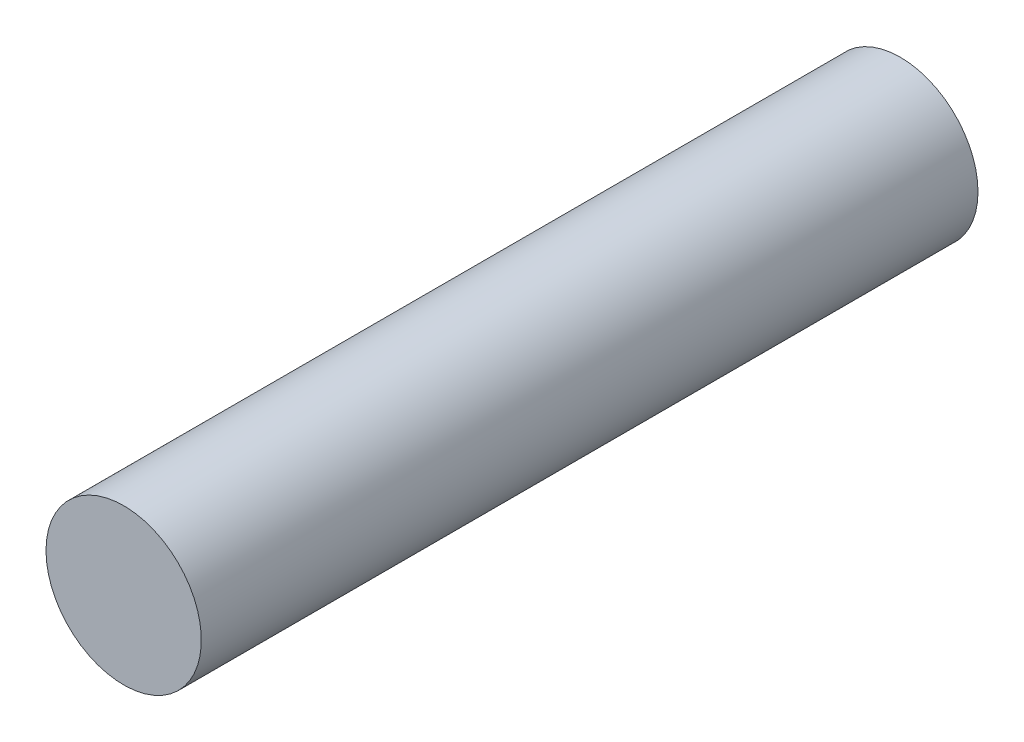
SolidWorks part; units mm, degrees
ref_plane "Front" through (0, 0, 0) normal (0, 0, 1) x (1, 0, 0)
ref_plane "Top" through (0, 0, 0) normal (0, 1, 0) x (1, 0, 0)
ref_plane "Right" through (0, 0, 0) normal (1, 0, 0) x (0, 0, -1)
sketch "Sketch2" plane through (0, 0, 0) normal (0, 0, 1) x (1, 0, 0)
  circle A0 centre (0, 0) radius 7.62
  dimension "D1" = 15.24
extrude "Boss-Extrude1" add sketch "Sketch2" along normal blind 76.2
sketch "Sketch7" plane through (0, 0, 0) normal (0, 1, 0) x (1, 0, 0)
  line L0 (0, 0) -> (0, 2.5393)
  line L1 (0, 0) -> (7.62, 0)
  arc A0 (0, 2.5393) -> (7.62, 0) centre (0, -10.1633) cw
revolve "Revolve1" add sketch "Sketch7" angle 360 about L0
